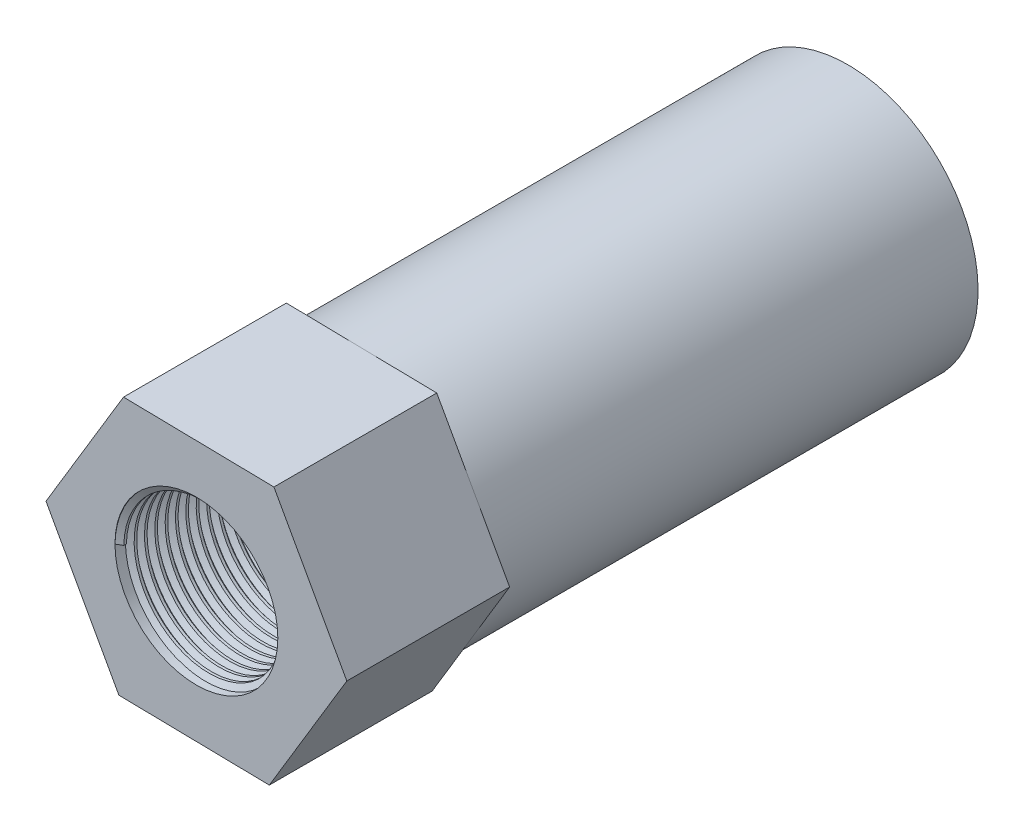
SolidWorks part; units mm, degrees
ref_plane "Front Plane" through (0, 0, 0) normal (0, 0, 1) x (1, 0, 0)
ref_plane "Top Plane" through (0, 0, 0) normal (0, 1, 0) x (1, 0, 0)
ref_plane "Right Plane" through (0, 0, 0) normal (1, 0, 0) x (0, 0, -1)
sketch "Sketch1" plane through (0, 0, 0) normal (0, 0, 1) x (1, 0, 0)
  line L1 (-2.3801, -3.9584) -> (2.238, -4.0404)
  line L2 (2.238, -4.0404) -> (4.6181, -0.082)
  line L3 (4.6181, -0.082) -> (2.3801, 3.9584)
  line L4 (2.3801, 3.9584) -> (-2.238, 4.0404)
  line L5 (-2.238, 4.0404) -> (-4.6181, 0.082)
  line L6 (-4.6181, 0.082) -> (-2.3801, -3.9584)
  circle A0 centre (0, 0) radius 4 construction
  dimension "D1" = 8
extrude "Boss-Extrude1" add sketch "Sketch1" along normal blind 5
sketch "Sketch2" plane through (0, 0, 0) normal (0, 0, -1) x (-1, 0, 0)
  circle A1 centre (0, 0) radius 4
  dimension "D1" = 8
extrude "Boss-Extrude2" add sketch "Sketch2" along normal blind 15
sketch "Sketch3" plane through (0, 0, 5) normal (0, 0, 1) x (1, 0, 0)
  circle A1 centre (0, 0) radius 2.5
  dimension "D1" = 5
extrude "Cut-Extrude1" cut sketch "Sketch3" against normal blind 5
thread "Thread1" pitch 0.3175 method extrude profile "Thread Profile2" start angle 0, offset 0, length 5, pitch 0.3175, diameter 5
ref_plane "Plane2" through (-2.5, 0, 5) normal (0, -1, 0) x (-1, 0, 0)
sketch "Thread Profile2" plane through (-2.5, 0, 5) normal (0, -1, 0) x (-1, 0, 0)
  line L0 (0, 0) -> (0, 0.3175) construction
  line L11 (0, 0) -> (0, 0.2778)
  line L12 (0, 0.2778) -> (-0.1719, 0.1786)
  line L13 (-0.1719, 0.1786) -> (-0.1719, 0.0992)
  line L15 (-0.1719, 0.0992) -> (0, 0)
  line L17 (-0.1719, 0.1389) -> (0, 0.1389) construction
  point P2 (0, 0)
  dimension "Pitch" = 0.3175
  dimension "Profile_Angle" = 60
  dimension "Profile_Land" = 0.0794
  dimension "Profile_Height" = 0.1719
sketch "Sketch8" plane through (0, 0, -15) normal (0, 0, -1) x (-1, 0, 0)
  circle A0 centre (0, 0) radius 2.5
  dimension "D1" = 5
extrude "Cut-Extrude2" cut sketch "Sketch8" against normal blind 5
thread "Thread2" pitch 0.3175 method extrude profile "Thread Profile3" start angle 0, offset 0, length 5, pitch 0.3175, diameter 5
ref_plane "Plane3" through (2.5, 0, -15) normal (0, -1, 0) x (1, 0, 0)
sketch "Thread Profile3" plane through (2.5, 0, -15) normal (0, -1, 0) x (1, 0, 0)
  line L0 (0, 0) -> (0, 0.3175) construction
  line L11 (0, 0) -> (0, 0.2778)
  line L12 (0, 0.2778) -> (-0.1719, 0.1786)
  line L13 (-0.1719, 0.1786) -> (-0.1719, 0.0992)
  line L15 (-0.1719, 0.0992) -> (0, 0)
  line L17 (-0.1719, 0.1389) -> (0, 0.1389) construction
  point P2 (0, 0)
  dimension "Pitch" = 0.3175
  dimension "Profile_Angle" = 60
  dimension "Profile_Land" = 0.0794
  dimension "Profile_Height" = 0.1719
